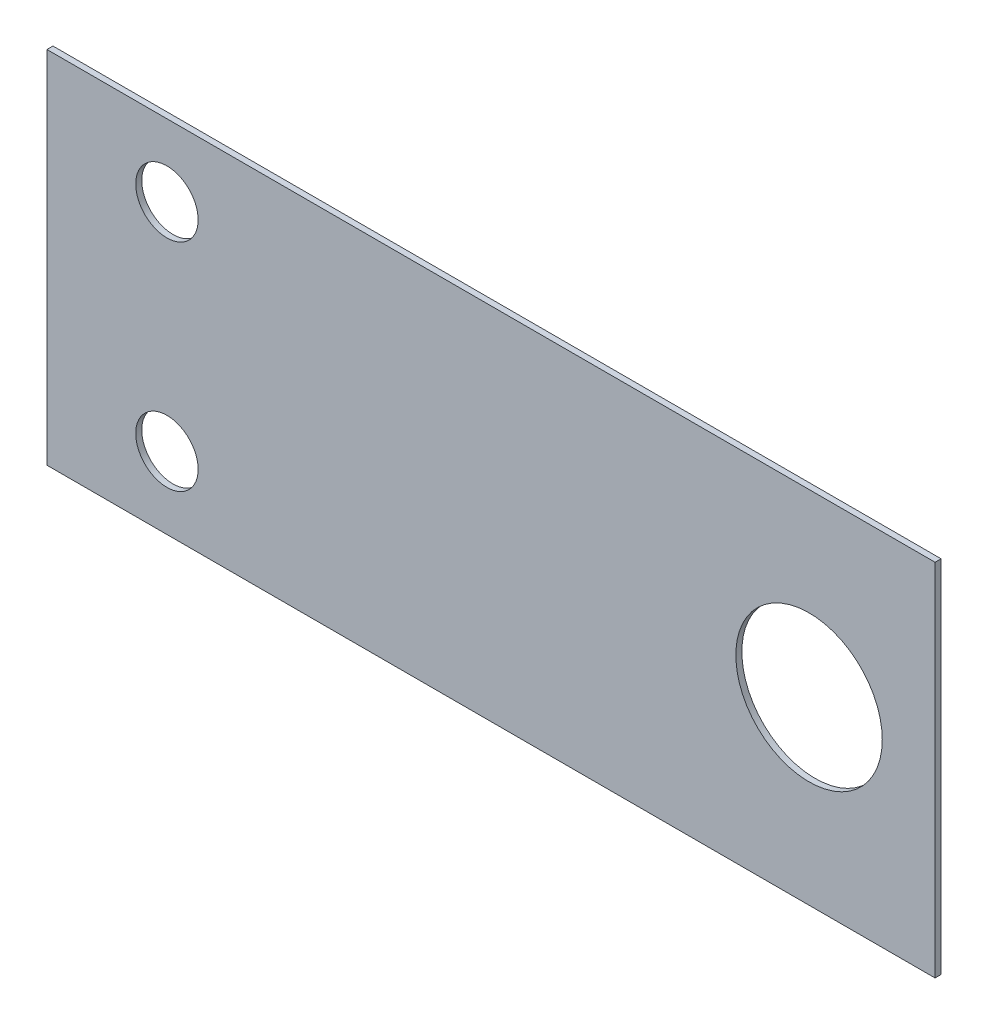
SolidWorks part; units mm, degrees
ref_plane "Front Plane" through (0, 0, 0) normal (0, 0, 1) x (1, 0, 0)
ref_plane "Top Plane" through (0, 0, 0) normal (0, 1, 0) x (1, 0, 0)
ref_plane "Right Plane" through (0, 0, 0) normal (1, 0, 0) x (0, 0, -1)
sketch "Sketch1" plane through (0, 0, 0) normal (0, 0, 1) x (1, 0, 0)
  line L1 (-37, -15) -> (37, -15)
  line L2 (-37, -15) -> (-37, 15)
  line L3 (-37, 15) -> (37, 15)
  line L4 (37, -15) -> (37, 15)
  line L5 (-37, -15) -> (37, 15) construction
  line L6 (-37, 15) -> (37, -15) construction
  point P0 (0, 0)
  dimension "D1" = 74
  dimension "D2" = 30
base flange "Base-Flange1" sketch "Sketch1" thickness 0.5 reverse thickness direction yes parameters "D1"=0.2286
hole_wizard "Ø5.2 (5.2) Diameter Hole1" positions "Sketch7" profile "Sketch8" hole size "Ø5.2" standard "DIN" end condition through all
sketch "Sketch7" plane through (0, 0, 0.5) normal (0, 0, 1) x (1, 0, 0)
  line L0 (-50.7737, 0) -> (49.9812, 0) construction
  line L2 (0, 36.2633) -> (0, -33.5081) construction
  line L4 (-37, 15) -> (-37, -15) construction
  point P0 (-27, 9)
  dimension "D1" = 18
  dimension "D2" = 10
sketch "Sketch8" plane through (-27, 9, 0.5) normal (1, 0, 0) x (0, -1, 0)
  line L0 (0, 0) -> (0, 0.5)
  line L1 (0, 0.5) -> (2.6, 0.5)
  line L2 (2.6, 0.5) -> (2.6, 0)
  line L5 (2.6, 0) -> (0, 0)
  line L11 (0, -6.35) -> (0, 107.95) construction
  dimension "Thru Hole Dia." = 5.2
  dimension "Thru Hole Depth" = 0.5
mirror "Mirror1" about plane through (0, 0, 0) normal (0, 1, 0) of "Ø5.2 (5.2) Diameter Hole1"
hole_wizard "Ø12.2 (12.2) Diameter Hole1" positions "Sketch10" profile "Sketch9" hole size "Ø12.2" standard "DIN" end condition through all
sketch "Sketch10" plane through (0, 0, 0.5) normal (0, 0, 1) x (1, 0, 0)
  line L0 (-50.0616, 0) -> (9.7357, 0) construction
  line L2 (-37, 15) -> (-37, -15) construction
  point P0 (26.5, 0)
  dimension "D1" = 63.5
sketch "Sketch9" plane through (26.5, 0, 0.5) normal (1, 0, 0) x (0, -1, 0)
  line L0 (0, 0) -> (0, 0.5)
  line L1 (0, 0.5) -> (6.1, 0.5)
  line L2 (6.1, 0.5) -> (6.1, 0)
  line L5 (6.1, 0) -> (0, 0)
  line L11 (0, -6.35) -> (0, 107.95) construction
  dimension "Thru Hole Dia." = 12.2
  dimension "Thru Hole Depth" = 0.5
sketch "Bend-Lines1" [suppressed] plane through (0, 0, 0) normal (0, 1, 0) x (1, 0, 0)
sketch "Bounding-Box1" [suppressed] plane through (0, 0, 0) normal (0, 1, 0) x (1, 0, 0)
sheet metal parameters "Sheet-Metal7" thickness 0.5 parameters "D1"=0.2286
flat pattern "Flat-Pattern7" [suppressed]
sketch "Bend-Lines2" plane through (0, 0, 0) normal (0, 1, 0) x (1, 0, 0)
sketch3d "Bounding-Box2" [suppressed]
  line L0 (-37, -15, 0) -> (37, -15, 0) construction
  line L1 (-37, 15, 0) -> (37, 15, 0) construction
  line L2 (-37, -15, 0) -> (-37, 15, 0) construction
  line L3 (37, -15, 0) -> (37, 15, 0) construction
sheet metal parameters "Sheet-Metal8" thickness 0.5 parameters "D1"=0.2286
flat pattern "Flat-Pattern7"
sketch "Bend-Lines2" plane through (0, 0, 0) normal (0, 1, 0) x (1, 0, 0)
sketch3d "Bounding-Box2" [suppressed]
  line L0 (37, -15, 0) -> (-37, -15, 0) construction
  line L1 (37, 15, 0) -> (-37, 15, 0) construction
  line L2 (37, -15, 0) -> (37, 15, 0) construction
  line L3 (-37, -15, 0) -> (-37, 15, 0) construction
sheet metal parameters "Sheet-Metal9" thickness 0.5 parameters "D1"=0.2286
flat pattern "Flat-Pattern7"
sketch "Bend-Lines2" plane through (0, 0, 0) normal (0, 1, 0) x (1, 0, 0)
sketch3d "Bounding-Box2" [suppressed]
  line L0 (37, -15, 0) -> (-37, -15, 0) construction
  line L1 (37, 15, 0) -> (-37, 15, 0) construction
  line L2 (37, -15, 0) -> (37, 15, 0) construction
  line L3 (-37, -15, 0) -> (-37, 15, 0) construction
sheet metal parameters "Sheet-Metal10" thickness 0.5 parameters "D1"=0.2286
flat pattern "Flat-Pattern7"
sketch "Bend-Lines2" plane through (0, 0, 0) normal (0, 1, 0) x (1, 0, 0)
sketch3d "Bounding-Box2" [suppressed]
  line L0 (37, -15, 0) -> (-37, -15, 0) construction
  line L1 (37, 15, 0) -> (-37, 15, 0) construction
  line L2 (37, -15, 0) -> (37, 15, 0) construction
  line L3 (-37, -15, 0) -> (-37, 15, 0) construction
